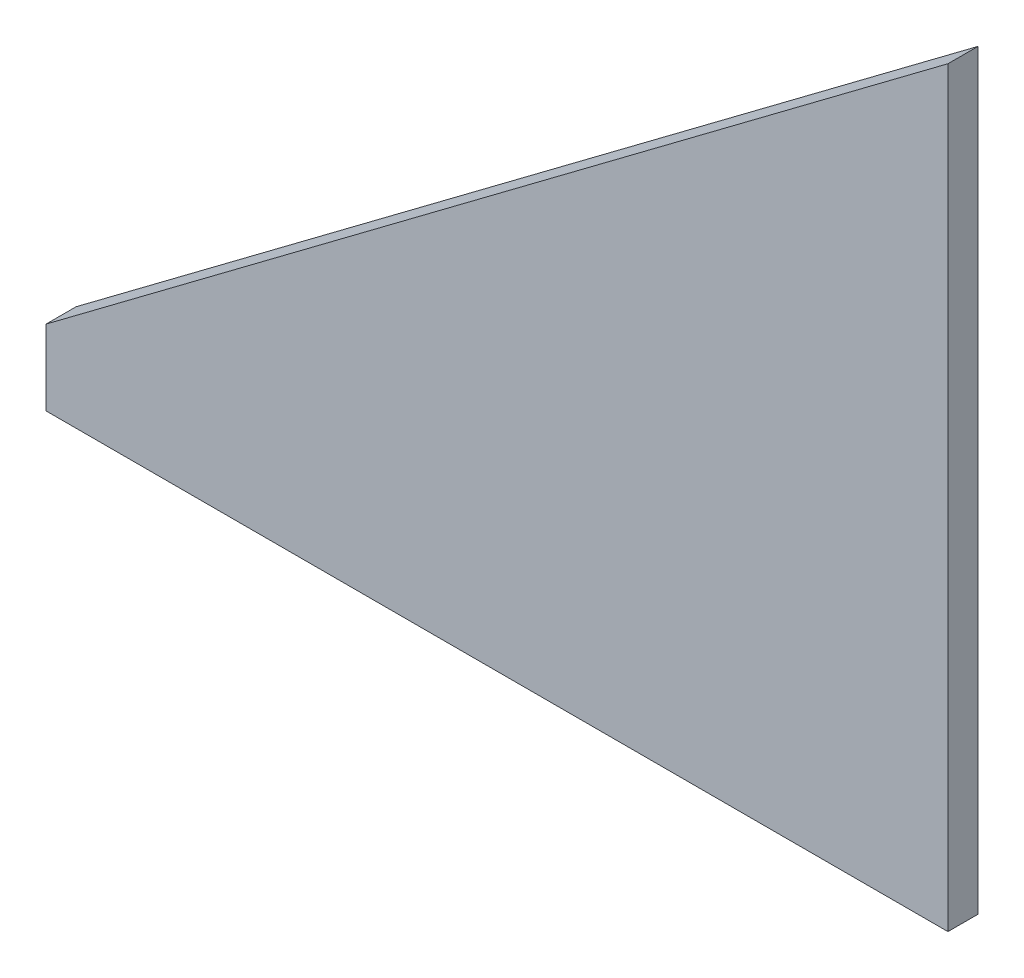
SolidWorks part; units mm, degrees
material "SA-283 Gr.C"
ref_plane "Front Plane" through (0, 0, 0) normal (0, 0, 1) x (1, 0, 0)
ref_plane "Top Plane" through (0, 0, 0) normal (0, 1, 0) x (1, 0, 0)
ref_plane "Right Plane" through (0, 0, 0) normal (1, 0, 0) x (0, 0, -1)
sketch "Sketch1" plane through (0, 0, 0) normal (0, 0, 1) x (1, 0, 0)
  line B0 (-350, -1707.9635) -> (-650, -1932.9635)
  line B1 (-650, -1932.9635) -> (-650, -1957.9635)
  line B2 (-650, -1957.9635) -> (-350, -1957.9635)
  line B3 (-350, -1957.9635) -> (-350, -1707.9635)
sketch_block_instance "Silencer support 2-1"
sketch_block "Silencer support 2" parameters "D1"=300, "D2"=250, "D3"=25
extrude "Boss-Extrude1" add sketch "Sketch1" along normal blind 10 contours B2 B3 B0 B1 region at (-459.0909, -1873.8726, 0)
